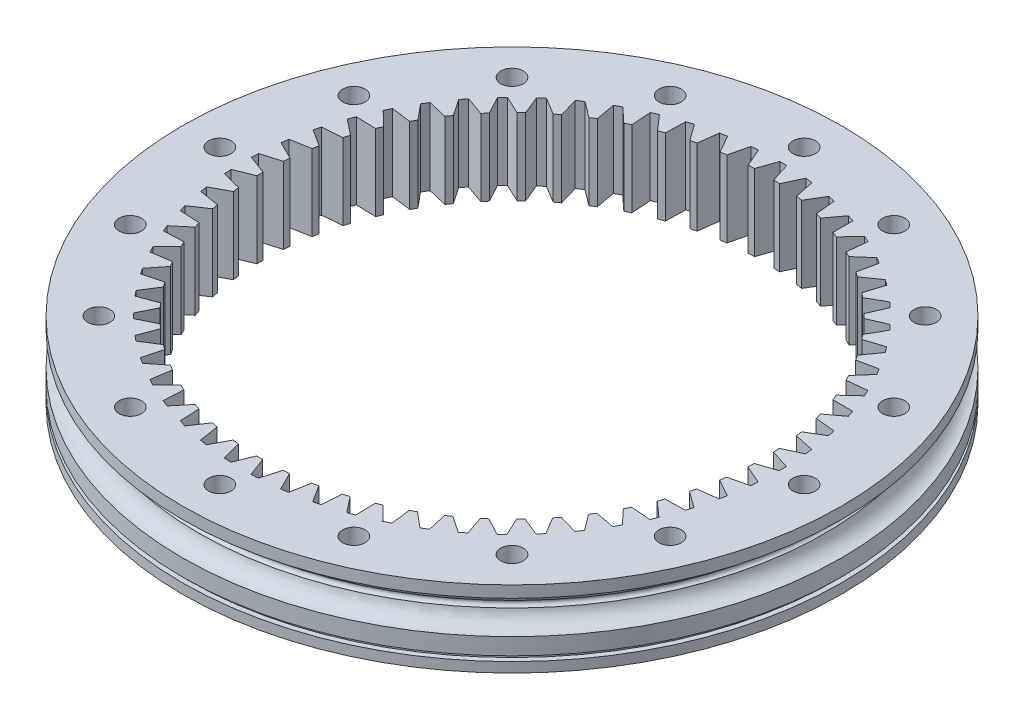
SolidWorks part; units mm, degrees
ref_plane "Plan de face" through (0, 0, 0) normal (0, 0, 1) x (1, 0, 0)
ref_plane "Plan de dessus" through (0, 0, 0) normal (0, 1, 0) x (1, 0, 0)
ref_plane "Plan de droite" through (0, 0, 0) normal (1, 0, 0) x (0, 0, -1)
sketch "Esquisse1" plane through (0, 0, 0) normal (0, 0, 1) x (1, 0, 0)
  line L0 (0, 0) -> (-237.5, 0) construction
  line L1 (-237.5, 0) -> (-237.5, 46) construction
  line L2 (-237.5, 46) -> (0, 46) construction
  line L3 (0, 46) -> (0, 0) construction
  line L4 (-237.5, 0) -> (-200.5, 0) construction
  line L5 (-200.5, 0) -> (-200.5, 10) construction
  line L6 (-200.5, 10) -> (-200.5, 30) construction
  line L7 (-200.5, 46) -> (-200.5, 40) construction
  line L8 (-200.5, 46) -> (-237.5, 46) construction
  line L9 (-200.5, 20) -> (-210, 20) construction
  line L10 (-210, 20) -> (-212, 20) construction
  line L11 (-200.5, 40) -> (-203.5, 40) construction
  line L12 (-203.5, 40) -> (-203.5, 37) construction
  line L13 (-203.5, 37) -> (-200.5, 37) construction
  line L14 (-200.5, 37) -> (-200.5, 30) construction
  line L15 (-200.5, 40) -> (-200.5, 37) construction
  line L16 (-199.5, 46) -> (-199.5, 0) construction
  line L17 (-198.5, 30) -> (-198.5, 37)
  line L18 (-198.5, 37) -> (-150, 37)
  line L19 (-150, 37) -> (-150, -9)
  line L20 (-150, -9) -> (-198.5, -9)
  line L21 (-198.5, -9) -> (-198.5, -3)
  line L22 (-198.5, -3) -> (-198.5, 0) construction
  line L23 (-198.5, 0) -> (-198.5, 10)
  line L24 (-198.5, 0) -> (-195.5, 0)
  line L25 (-195.5, 0) -> (-195.5, -3)
  line L26 (-195.5, -3) -> (-198.5, -3)
  line L27 (-200.5, 37) -> (-198.5, 37) construction
  arc A0 (-200.5, 30) -> (-200.5, 10) centre (-200.5, 20) ccw construction
  arc A1 (-210.3026, 21.977) -> (-210.3026, 18.023) centre (-210, 20) ccw construction
  arc A2 (-210.3026, 18.023) -> (-200.5, 10) centre (-200.5, 20) ccw construction
  arc A3 (-200.5, 30) -> (-210.3026, 21.977) centre (-200.5, 20) ccw construction
  arc A4 (-188.6974, 21.977) -> (-188.6974, 18.023) centre (-189, 20) cw
  arc A5 (-198.5, 30) -> (-198.5, 10) centre (-198.5, 20) cw construction
  arc A6 (-198.5, 30) -> (-188.6974, 21.977) centre (-198.5, 20) cw
  arc A7 (-188.6974, 18.023) -> (-198.5, 10) centre (-198.5, 20) cw
  dimension "D1" = 200.5
  dimension "D7" = 10
  dimension "D8" = 9.5
  dimension "D9" = 2
  dimension "D2" = 46
  dimension "D3" = 20
  dimension "D4" = 9
  dimension "D5" = 3
  dimension "D6" = 3
  dimension "D10" = 237.5
  dimension "D11" = 1
  dimension "D12" = 3
  dimension "D13" = 3
  dimension "D14" = 46
  dimension "D15" = 300
revolve "Révolution1" add sketch "Esquisse1" angle 360 about L3
sketch "Esquisse4" plane through (0, 37, 0) normal (0, 1, 0) x (1, 0, 0)
  line L0 (0, 0) -> (-176, 0) construction
  line L1 (0, 0) -> (-162.6028, 67.3523) construction
  circle A0 centre (-176, 0) radius 6.75
  circle A1 centre (-162.6028, 67.3523) radius 6.75
  circle A2 centre (-124.4508, 124.4508) radius 6.75
  circle A3 centre (-67.3523, 162.6028) radius 6.75
  circle A4 centre (0, 176) radius 6.75
  circle A5 centre (67.3523, 162.6028) radius 6.75
  circle A6 centre (124.4508, 124.4508) radius 6.75
  circle A7 centre (162.6028, 67.3523) radius 6.75
  circle A8 centre (176, 0) radius 6.75
  circle A9 centre (162.6028, -67.3523) radius 6.75
  circle A10 centre (124.4508, -124.4508) radius 6.75
  circle A11 centre (67.3523, -162.6028) radius 6.75
  circle A12 centre (0, -176) radius 6.75
  circle A13 centre (-67.3523, -162.6028) radius 6.75
  circle A14 centre (-124.4508, -124.4508) radius 6.75
  circle A15 centre (-162.6028, -67.3523) radius 6.75
  point P38 (0, 0)
  dimension "D1" = 13.5
  dimension "D2" = 176
  dimension "D4" = 22.5
  dimension "D5" = 176
  dimension "D3" = 16
extrude "Enlèv. mat.-Extru.2" cut sketch "Esquisse4" against normal through all
sketch "Esquisse5" plane through (0, 37, 0) normal (0, 1, 0) x (1, 0, 0)
  line L0 (0, 0) -> (-161.25, 0) construction
  line L1 (0, 0) -> (-161.029, 8.4392) construction
  line L2 (0, 0) -> (-160.3667, 16.8552) construction
  line L3 (-149.1783, 15.6793) -> (-144.4927, 15.1868)
  line L4 (-144.4927, 15.1868) -> (-144.4927, 0)
  line L5 (-144.4927, 0) -> (-150, 0)
  line L6 (-149.1783, 15.6793) -> (-149.5376, 11.7689)
  line L7 (-149.5376, 11.7689) -> (-161.029, 8.4392)
  line L8 (-161.029, 8.4392) -> (-161.1947, 4.221)
  line L9 (-161.1947, 4.221) -> (-150, 0)
  line L10 (-149.5376, 11.7689) -> (0, 0) construction
  line L11 (0, 0) -> (-161.029, 8.4392) construction
  line L12 (-161.1947, 4.221) -> (0, 0) construction
  circle A0 centre (0, 0) radius 161.25 construction
  circle A1 centre (0, 0) radius 150 construction
  circle A2 centre (0, 0) radius 152.5 construction
  circle A3 centre (0, 0) radius 150 construction
  point P8 (-150, 0)
  point P9 (-149.1783, 15.6793)
  circle M18 centre (0, 0) radius 150
  dimension "D1" = 300
  dimension "D2" = 305
  dimension "D3" = 11.25
  dimension "D4" = 6
  dimension "D5" = 3
  dimension "D6" = 1.5
  dimension "D7" = 1.5
  dimension "D8" = 1.5
extrude "Enlèv. mat.-Extru.3" cut sketch "Esquisse5" against normal through all contours L3 L6 L5 L4 M18 | L8 L9 L7 M18 region at (-147.1295, 37, -7.5196) region at (-154.5952, 37, -6.0741)
ref_axis "Axe1" through (0, 39.3, 0) along (0, -1, 0)
pattern_circular "Répétition circulaire1" count 61 over 360 about axis through (0, 39.3, 0) along (0, -1, 0) of "Enlèv. mat.-Extru.3"
